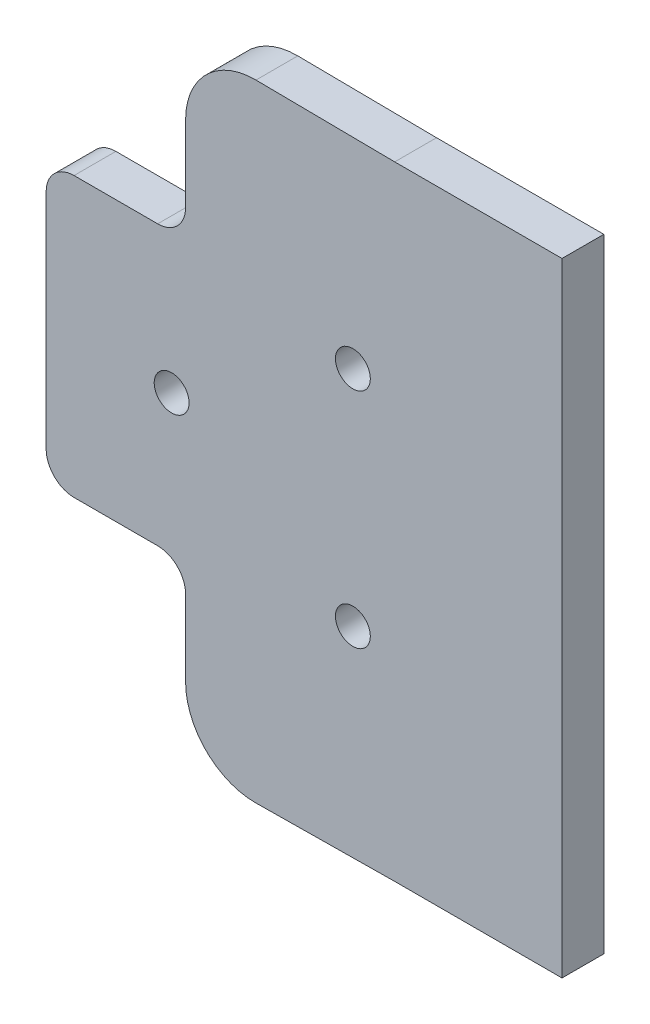
SolidWorks part; units mm, degrees
ref_plane "Front Plane" through (0, 0, 0) normal (0, 0, 1) x (1, 0, 0)
ref_plane "Top Plane" through (0, 0, 0) normal (0, 1, 0) x (1, 0, 0)
ref_plane "Right Plane" through (0, 0, 0) normal (1, 0, 0) x (0, 0, -1)
sketch "Sketch1" plane through (0, 0, 0) normal (0, 0, 1) x (1, 0, 0)
  line L12 (1.0833, 19.8763) -> (1.0833, 14.4203)
  line L17 (-0.9167, 12.4203) -> (-6.9167, 12.4203)
  line L18 (-8.9167, 10.4203) -> (-8.9167, -5.5797)
  line L19 (-6.9167, -7.5797) -> (-0.9167, -7.5797)
  line L20 (1.0833, -9.5797) -> (1.0833, -15.0358)
  line L23 (16.0833, 24.7682) -> (28.0833, 24.7682)
  line L25 (16.0833, -19.9276) -> (28.0833, -19.9276)
  line L26 (28.0833, 24.7682) -> (28.0833, -19.9276)
  arc A18 (6.1318, 24.8761) -> (1.0833, 19.8763) centre (6.0833, 19.8763) ccw
  arc A19 (-0.9167, 12.4203) -> (1.0833, 14.4203) centre (-0.9167, 14.4203) ccw
  arc A20 (-6.9167, 12.4203) -> (-8.9167, 10.4203) centre (-6.9167, 10.4203) ccw
  arc A21 (-8.9167, -5.5797) -> (-6.9167, -7.5797) centre (-6.9167, -5.5797) ccw
  arc A22 (1.0833, -9.5797) -> (-0.9167, -7.5797) centre (-0.9167, -9.5797) ccw
  arc A23 (1.0833, -15.0358) -> (6.1318, -20.0355) centre (6.0833, -15.0358) ccw
  circle A24 centre (13.0833, 10.4203) radius 1.25
  circle A25 centre (13.0833, 10.4203) radius 2.15
  circle A26 centre (0.0833, 2.4203) radius 1.25
  circle A27 centre (0.0833, 2.4203) radius 2.15
  circle A28 centre (13.0833, -5.5797) radius 2.15
  circle A29 centre (13.0833, -5.5797) radius 1.25
  spline S0 degree 3 poles (16.0833, 24.7682) (12.5708, 24.8091) (9.2481, 24.8459) (6.1318, 24.8761) knots 0.046328 0.046328 0.046328 0.046328 0.128883 0.128883 0.128883 0.128883
  spline S1 degree 3 poles (6.1318, -20.0355) (9.2481, -20.0053) (12.5708, -19.9686) (16.0833, -19.9276) knots 0.046328 0.046328 0.046328 0.046328 0.128883 0.128883 0.128883 0.128883
  dimension "D1" = 12
extrude "Boss-Extrude1" add sketch "Sketch1" along normal mid plane 3 contours S0 | A23 S1 L25 L26 L23 S0 A18 L12 A19 L17 A20 L18 A21 L19 A22 L20 A25 A27 A28 | A27 A26 | A28 A29 | A25 A24 region at (12.1363, 2.4203, 0) region at (10.9941, 10.4203, 0) region at (-2.0059, 2.4203, 0) region at (10.9941, -5.5797, 0)
